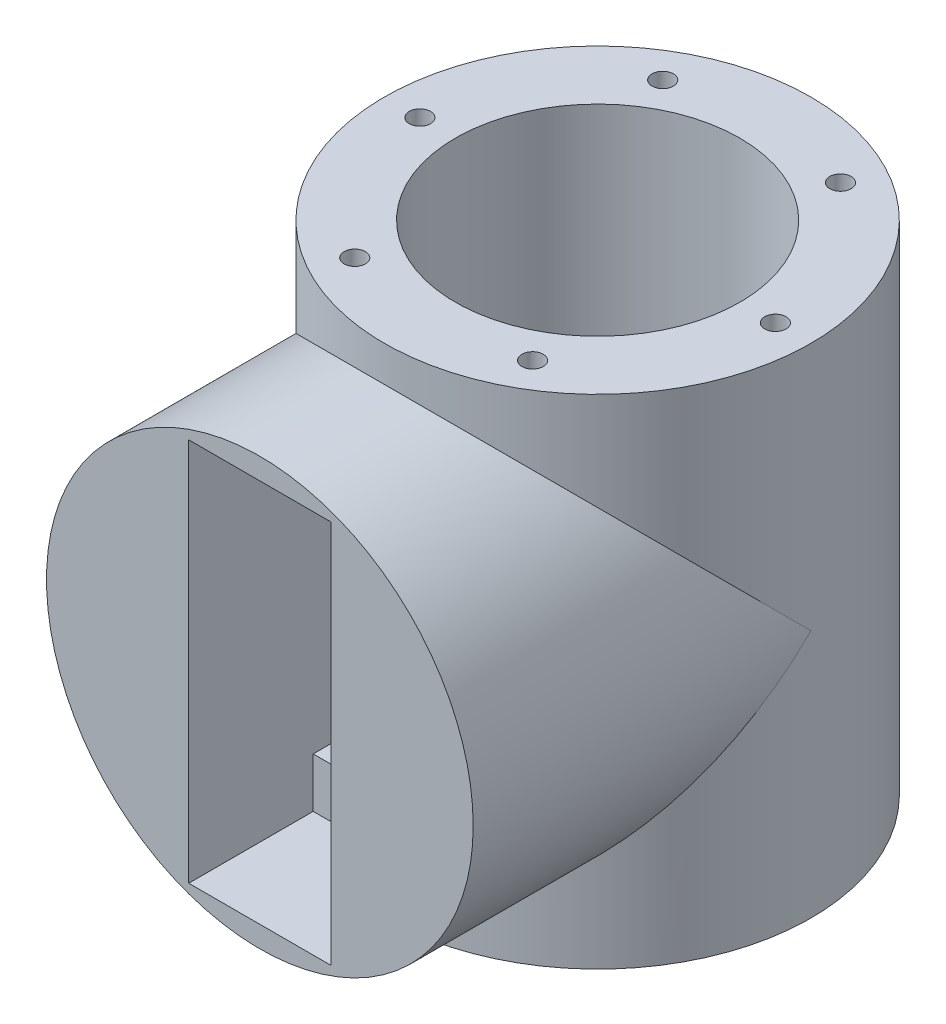
SolidWorks part; units mm, degrees
ref_plane "Спереди" through (0, 0, 0) normal (0, 0, 1) x (1, 0, 0)
ref_plane "Сверху" through (0, 0, 0) normal (0, 1, 0) x (1, 0, 0)
ref_plane "Справа" through (0, 0, 0) normal (1, 0, 0) x (0, 0, -1)
sketch "Эскиз6" plane through (0, 0, 0) normal (1, 0, 0) x (0, 0, -1)
  line L0 (26, 0) -> (30, 0)
  line L1 (0, 0) -> (0, 55.3682) construction
  line L2 (30, 0) -> (30, 70)
  line L3 (30, 70) -> (20, 70)
  line L4 (20, 70) -> (20, 12)
  line L5 (20, 12) -> (0, 12)
  line L6 (0, 12) -> (0, 7)
  line L7 (0, 7) -> (26, 7)
  line L8 (26, 7) -> (26, 0)
  point P5 (0, 0)
revolve "Повернуть1" add sketch "Эскиз6" angle 360 about L1
sketch "Эскиз9" plane through (0, 0, 0) normal (0, 1, 0) x (1, 0, 0)
  circle A0 centre (0, 0) radius 3
  circle A1 centre (0, 0) radius 7 construction
  circle A2 centre (0, 7) radius 1.5
  circle A3 centre (7, 0) radius 1.5
  circle A4 centre (0, -7) radius 1.5
  circle A5 centre (-7, 0) radius 1.5
  point P15 (0, 0)
  dimension "D1" = 4
extrude "Вырез-Вытянуть1" cut sketch "Эскиз9" along normal up to surface (12 mm away) from offset 7 up to face at (0, 12, -20)
sketch "Эскиз10" plane through (0, 0, 0) normal (0, 0, 1) x (1, 0, 0)
  line L0 (-30, 0) -> (30, 0) construction
  circle A0 centre (0, 35) radius 30
  dimension "D1" = 60
  dimension "D2" = 35
extrude "Бобышка-Вытянуть5" add sketch "Эскиз10" along normal blind 17.5 and the other way up to surface from offset 30 other way up to face at (0, 70, -30)
ref_plane "Плоскость1" through (0, 0, 47.5) normal (0, 0, 1) x (1, 0, 0)
sketch "Эскиз11" plane through (0, 0, 47.5) normal (0, 0, 1) x (1, 0, 0)
  line L0 (-30, 0) -> (30, 0) construction
  line L1 (-10, 55) -> (10, 55)
  line L2 (-10, 55) -> (-10, 15)
  line L3 (-10, 15) -> (10, 15)
  line L4 (10, 55) -> (10, 15)
  dimension "D1" = 40
  dimension "D2" = 20
  dimension "D3" = 15
extrude "Вырез-Вытянуть2" cut sketch "Эскиз11" against normal up to surface (30.1795 mm away) up to face at (0, 12, -20)
sketch "Эскиз12" plane through (0, 0, 47.5) normal (0, 0, 1) x (1, 0, 0)
  line L1 (-10, 62) -> (10, 62)
  line L2 (-10, 62) -> (-10, 8)
  line L3 (-10, 8) -> (10, 8)
  line L4 (10, 62) -> (10, 8)
  line L5 (-10, 55) -> (-10, 15) construction
  line L7 (30, 70) -> (-30, 70) construction
  point P6 (-10, 60)
  point P7 (10, 20)
  point P8 (0, 0)
  point P9 (0, 0)
  dimension "D3" = 8
  dimension "D1" = 54
  dimension "D2" = 20
extrude "Вырез-Вытянуть3" cut sketch "Эскиз12" against normal blind 17.5
sketch "Эскиз13" plane through (0, 0, 0) normal (0, 1, 0) x (1, 0, 0)
  circle A0 centre (-25, 0) radius 1.5
  dimension "D1" = 3
  dimension "D2" = 25
extrude "Вырез-Вытянуть4" cut sketch "Эскиз13" against normal blind 7 from offset 70
pattern_circular "Круговой массив1" count 6 every 60 about axis through (0, 70, 0) along (0, -1, 0) of "Вырез-Вытянуть4"
